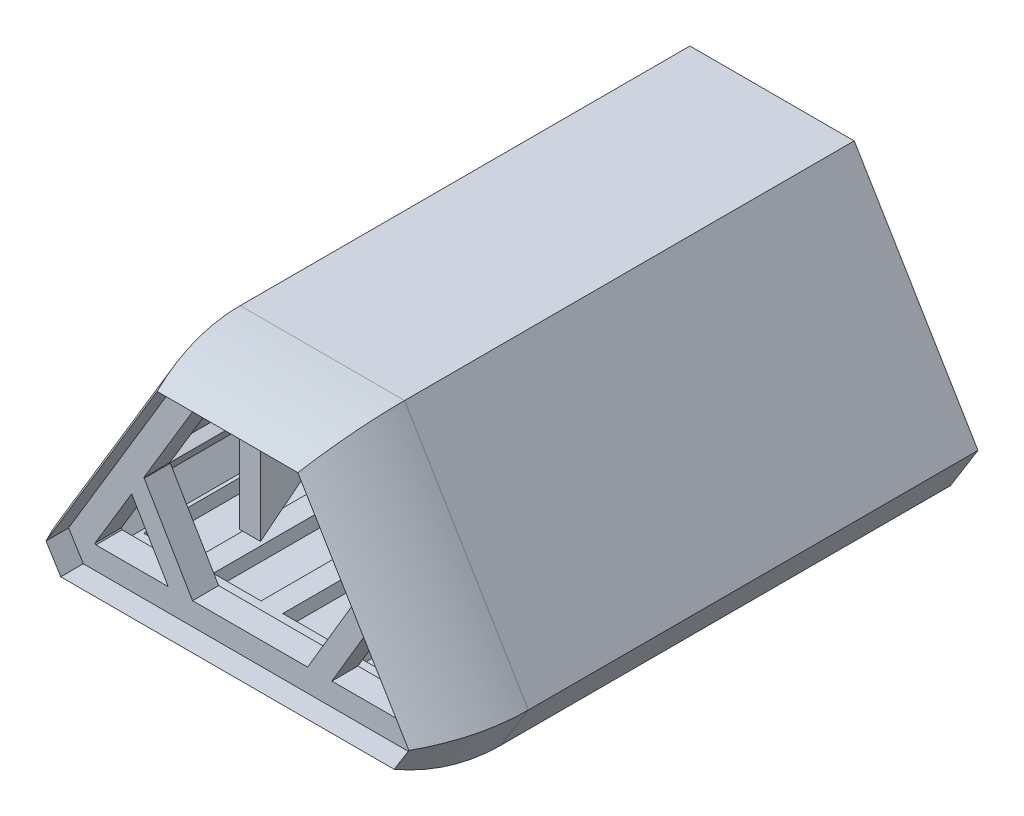
SolidWorks part; units mm, degrees
ref_plane "Front Plane" through (0, 0, 0) normal (0, 0, 1) x (1, 0, 0)
ref_plane "Top Plane" through (0, 0, 0) normal (0, 1, 0) x (1, 0, 0)
ref_plane "Right Plane" through (0, 0, 0) normal (1, 0, 0) x (0, 0, -1)
sketch "Sketch1" plane through (0, 0, 0) normal (0, 0, 1) x (1, 0, 0)
  line L0 (-24.4756, -10.0139) -> (-21.1802, -15.312)
  line L1 (-21.4286, -9.9899) -> (-19.7355, -12.712)
  line L2 (-19.7355, -12.712) -> (18.5963, -12.712)
  line L3 (18.5963, -12.712) -> (20.2895, -9.9899)
  line L4 (20.2895, -9.9899) -> (7.5154, 11.288)
  line L5 (7.5154, 11.288) -> (-8.6546, 11.288)
  line L6 (-8.6546, 11.288) -> (-21.4286, -9.9899)
  line L7 (-21.1802, -15.312) -> (20.041, -15.312)
  line L8 (20.041, -15.312) -> (23.3365, -10.0139)
  line L9 (23.3365, -10.0139) -> (8.9871, 13.888)
  line L10 (8.9871, 13.888) -> (-10.1263, 13.888)
  line L11 (-10.1263, 13.888) -> (-24.4756, -10.0139)
  dimension "D1" = 2.6
extrude "Boss-Extrude1" add sketch "Sketch1" along normal blind 62.6
sketch "Sketch2" plane through (0, 0, 62.6) normal (0, 0, 1) x (1, 0, 0)
  line L6 (-8.6546, 11.288) -> (-21.4286, -9.9899)
  line L7 (-21.4286, -9.9899) -> (-19.7355, -12.712)
  line L8 (-19.7355, -12.712) -> (18.5963, -12.712)
  line L9 (18.5963, -12.712) -> (20.2895, -9.9899)
  line L10 (20.2895, -9.9899) -> (7.5154, 11.288)
  line L11 (7.5154, 11.288) -> (-8.6546, 11.288)
  line L12 (-7.1829, 8.688) -> (-18.3817, -9.9658)
  line L13 (-18.3817, -9.9658) -> (-18.2908, -10.112)
  line L14 (-18.2908, -10.112) -> (17.1516, -10.112)
  line L15 (17.1516, -10.112) -> (17.2425, -9.9658)
  line L16 (17.2425, -9.9658) -> (6.0438, 8.688)
  line L17 (6.0438, 8.688) -> (-7.1829, 8.688)
  line L18 (-7.1829, 8.688) -> (-18.3817, -9.9658)
  line L19 (-18.3817, -9.9658) -> (-18.2908, -10.112)
  line L20 (-18.2908, -10.112) -> (17.1516, -10.112)
  line L21 (17.1516, -10.112) -> (17.2425, -9.9658)
  line L22 (17.2425, -9.9658) -> (6.0438, 8.688)
  line L23 (6.0438, 8.688) -> (-7.1829, 8.688)
  dimension "D1" = 2.6
  dimension "D2" = 2.6
extrude "Boss-Extrude2" add sketch "Sketch2" against normal blind 5.6
sketch "Sketch4" plane through (0, 0, 62.6) normal (0, 0, 1) x (1, 0, 0)
  line L21 (6.0438, 8.688) -> (-7.1829, 8.688)
  line L22 (-7.1829, 8.688) -> (-18.3817, -9.9658)
  line L23 (-18.3817, -9.9658) -> (-18.2908, -10.112)
  line L24 (-18.2908, -10.112) -> (17.1516, -10.112)
  line L25 (17.1516, -10.112) -> (17.2425, -9.9658)
  line L26 (17.2425, -9.9658) -> (6.0438, 8.688)
  line L27 (7.5154, 11.288) -> (-8.6546, 11.288)
  line L28 (20.2895, -9.9899) -> (7.5154, 11.288)
  line L29 (18.5963, -12.712) -> (20.2895, -9.9899)
  line L30 (-19.7355, -12.712) -> (18.5963, -12.712)
  line L31 (-21.4286, -9.9899) -> (-19.7355, -12.712)
  line L32 (-8.6546, 11.288) -> (-21.4286, -9.9899)
  line L33 (7.5154, 11.288) -> (-8.6546, 11.288)
  line L34 (20.2895, -9.9899) -> (7.5154, 11.288)
  line L35 (18.5963, -12.712) -> (20.2895, -9.9899)
  line L36 (-19.7355, -12.712) -> (18.5963, -12.712)
  line L37 (-21.4286, -9.9899) -> (-19.7355, -12.712)
  line L38 (-8.6546, 11.288) -> (-21.4286, -9.9899)
  dimension "D1" = 2.6
  dimension "D2" = 2.6
extrude "Cut-Extrude1" cut sketch "Sketch4" against normal blind 2.6
chamfer "Chamfer1" distance 5 distance2 2.6 6 edges at (-22.8279, -12.6629, 62.6) (-0.5696, -15.312, 62.6) (21.6887, -12.6629, 62.6) (16.1618, 1.9371, 62.6) (-0.5696, 13.888, 62.6) (-17.3009, 1.9371, 62.6) first distance on face at (-22.8279, -12.6629, 31.3) first distance on face at (-0.5696, -15.312, 31.3) first distance on face at (21.6887, -12.6629, 31.3) first distance on face at (16.1618, 1.9371, 31.3) first distance on face at (-0.5696, 13.888, 31.3) first distance on face at (-17.3009, 1.9371, 31.3)
sketch "Sketch7" plane through (0, 0, 60) normal (0, 0, 1) x (1, 0, 0)
  line L0 (-1.7696, 11.288) -> (-1.7696, -0.312)
  line L1 (-1.7696, 11.288) -> (0.6304, 11.288)
  line L2 (7.5154, 11.288) -> (-8.6546, 11.288) construction
  line L3 (-1.7696, -0.312) -> (0.6304, -0.312)
  line L4 (0.6304, -0.312) -> (0.6304, 11.288)
  point P9 (-0.5696, -0.312)
  dimension "D1" = 11.6
extrude "Boss-Extrude3" add sketch "Sketch7" against normal blind 14.6
sketch "Sketch8" plane through (0.6304, 0, 0) normal (1, 0, 0) x (0, 0, -1)
  line L0 (-45.4, -0.312) -> (-45.4, 11.288)
  line L1 (-45.4, -0.312) -> (-60, -0.312) construction
  line L2 (-45.4, -0.312) -> (-45.4, 11.288) construction
  line L3 (-45.4, 11.288) -> (-60, -0.312)
  line L4 (-60, 8.688) -> (-60, -9.9658) construction
  line L5 (-60, -0.312) -> (-45.4, -0.312)
extrude "Cut-Extrude2" cut sketch "Sketch8" against normal blind 5.6
sketch "Sketch9" plane through (0, 0, 60) normal (0, 0, 1) x (1, 0, 0)
  line L0 (13.0469, -2.9772) -> (8.8314, -10.112)
  line L1 (-14.1861, -2.9772) -> (-14.8224, -2.5851)
  line L2 (-18.2908, -10.112) -> (17.1516, -10.112) construction
  line L3 (-12.7368, -0.712) -> (-7.1829, -10.112)
  line L4 (11.6431, -0.6389) -> (6.0438, -10.112)
  line L5 (-9.9705, -10.112) -> (-14.1861, -2.9772)
  line L6 (-14.8224, -2.5851) -> (-13.3476, -0.1914)
  line L7 (-7.1829, 8.688) -> (-18.3817, -9.9658) construction
  line L8 (-13.3476, -0.1914) -> (-12.7368, -0.712)
  line L9 (-9.9705, -10.112) -> (-9.9705, -10.7546)
  line L10 (-9.9705, -10.7546) -> (-6.6285, -10.7546)
  line L11 (17.2425, -9.9658) -> (6.0438, 8.688) construction
  line L12 (-6.6285, -10.7546) -> (-7.1829, -10.112)
  line L13 (8.8314, -10.112) -> (9.2111, -10.7546)
  line L14 (9.2111, -10.7546) -> (5.8074, -10.7546)
  line L15 (5.8074, -10.7546) -> (6.0438, -10.112)
  line L16 (13.0469, -2.9772) -> (13.7146, -2.3095)
  line L17 (13.7146, -2.3095) -> (11.9023, -0.4971)
  line L18 (11.9023, -0.4971) -> (11.6431, -0.6389)
extrude "Boss-Extrude11" add sketch "Sketch9" against normal blind 3
sketch "Sketch10" plane through (0, 0, 0) normal (0, 0, -1) x (-1, 0, 0)
  line L12 (24.4756, -10.0139) -> (10.1263, 13.888)
  line L13 (10.1263, 13.888) -> (-8.9871, 13.888)
  line L14 (-8.9871, 13.888) -> (-23.3365, -10.0139)
  line L15 (-23.3365, -10.0139) -> (-20.041, -15.312)
  line L16 (-20.041, -15.312) -> (21.1802, -15.312)
  line L17 (21.1802, -15.312) -> (24.4756, -10.0139)
  line L18 (24.4756, -10.0139) -> (10.1263, 13.888)
  line L19 (10.1263, 13.888) -> (-8.9871, 13.888)
  line L20 (-8.9871, 13.888) -> (-23.3365, -10.0139)
  line L21 (-23.3365, -10.0139) -> (-20.041, -15.312)
  line L22 (-20.041, -15.312) -> (21.1802, -15.312)
  line L23 (21.1802, -15.312) -> (24.4756, -10.0139)
  line L30 (24.2412, -10.0121) -> (10.0131, 13.688)
  line L31 (10.0131, 13.688) -> (-8.8739, 13.688)
  line L32 (-8.8739, 13.688) -> (-23.1021, -10.0121)
  line L33 (-23.1021, -10.0121) -> (-19.9299, -15.112)
  line L34 (-19.9299, -15.112) -> (21.069, -15.112)
  line L35 (21.069, -15.112) -> (24.2412, -10.0121)
  line L36 (24.2412, -10.0121) -> (10.0131, 13.688)
  line L37 (10.0131, 13.688) -> (-8.8739, 13.688)
  line L38 (-8.8739, 13.688) -> (-23.1021, -10.0121)
  line L39 (-23.1021, -10.0121) -> (-19.9299, -15.112)
  line L40 (-19.9299, -15.112) -> (21.069, -15.112)
  line L41 (21.069, -15.112) -> (24.2412, -10.0121)
  dimension "D1" = 0
  dimension "D2" = 0.2
extrude "Cut-Extrude3" cut sketch "Sketch10" against normal blind 81
fillet "Fillet1" radius 26 6 edges at (21.516, -12.562, 57.9846) (-0.5696, -15.112, 57.9846) (-22.6551, -12.562, 57.9846) (-17.1271, 1.838, 57.9846) (-0.5696, 13.688, 57.9846) (15.988, 1.838, 57.9846)
sketch "Sketch11" plane through (0, -12.712, 0) normal (0, 1, 0) x (1, 0, 0)
  line L5 (-3.3196, -53.4909) -> (2.1804, -53.4909)
  line L6 (-3.3196, -53.4909) -> (-3.3196, -2.4909)
  line L7 (-3.3196, -2.4909) -> (2.1804, -2.4909)
  line L8 (2.1804, -53.4909) -> (2.1804, -2.4909)
  line L9 (-3.3196, -53.4909) -> (2.1804, -2.4909) construction
  line L10 (-3.3196, -2.4909) -> (2.1804, -53.4909) construction
  point P8 (-0.5696, -27.9909)
  dimension "D2" = 5.5
  dimension "D3" = 51
extrude "Cut-Extrude4" cut sketch "Sketch11" against normal blind 1.6
pattern_linear "LPattern1" count 3 spacing 8 along (1, 0, 0) count 3 spacing 8 along (-1, 0, 0) of "Cut-Extrude4"
sketch "Sketch12" plane through (-11.3431, 6.8097, 0) normal (0.8574, -0.5147, 0) x (0, 0, -1)
  line L0 (0, -7.1856) -> (-57, -7.1856) construction
  line L1 (0, 5.2233) -> (0, -19.5945) construction
  line L2 (-57, 5.2233) -> (-57, -19.5945) construction
  line L3 (-53.4909, -9.614) -> (-53.4909, -4.7572)
  line L4 (-53.4909, -4.7572) -> (-2.4909, -4.7572)
  line L6 (-53.4909, -9.614) -> (-2.4909, -9.614)
  line L7 (-2.4909, -4.7572) -> (-2.4909, -9.614)
  line L8 (-53.4909, -4.8523) -> (-2.4909, -9.614) construction
  line L9 (-53.4909, -9.519) -> (-2.4909, -4.7572) construction
  point P6 (-28.5, -7.1856)
extrude "Cut-Extrude5" cut sketch "Sketch12" against normal blind 1.6
pattern_linear "LPattern2" count 2 spacing 8 along (-0.5147, -0.8574, 0) count 2 spacing 8 along (0.5147, 0.8574, 0) of "Cut-Extrude5"
sketch "Sketch13" plane through (10.5057, 6.307, 0) normal (-0.8574, -0.5147, 0) x (0, 0, 1)
  line L0 (0, -6.5993) -> (57, -6.5993) construction
  line L1 (0, -19.0082) -> (0, 5.8097) construction
  line L2 (57, -19.0082) -> (57, 5.8097) construction
  line L3 (53.4909, -9.3493) -> (53.4909, -3.8493)
  line L4 (53.4909, -3.8493) -> (2.4909, -3.8493)
  line L6 (53.4909, -9.3493) -> (2.4909, -9.3493)
  line L7 (2.4909, -3.8493) -> (2.4909, -9.3493)
  line L8 (53.4909, -3.9569) -> (2.4909, -9.3493) construction
  line L9 (53.4909, -9.2416) -> (2.4909, -3.8493) construction
  point P6 (28.5, -6.5993)
  dimension "D1" = 5.5
extrude "Cut-Extrude6" cut sketch "Sketch13" against normal blind 1.6
pattern_linear "LPattern3" count 2 spacing 8 along (0.5147, -0.8574, 0) count 2 spacing 8 along (-0.5147, 0.8574, 0) of "Cut-Extrude6"
sketch "Sketch14" plane through (0, 11.288, 0) normal (0, -1, 0) x (1, 0, 0)
  line L2 (6.8804, 53.5494) -> (1.3804, 53.5494)
  line L4 (1.3804, 53.5494) -> (1.3804, 2.5494)
  line L5 (1.3804, 2.5494) -> (6.8804, 2.5494)
  line L6 (6.8804, 53.5494) -> (6.8804, 2.5494)
  line L7 (1.6964, 53.5494) -> (6.8804, 2.5494) construction
  line L8 (1.3804, 2.5494) -> (6.5645, 53.5494) construction
  line L10 (-2.5604, 53.5615) -> (-8.0604, 53.5615)
  line L11 (-8.0604, 53.5615) -> (-8.0604, 2.5615)
  line L12 (-8.0604, 2.5615) -> (-2.5604, 2.5615)
  line L13 (-2.5604, 53.5615) -> (-2.5604, 2.5615)
  line L14 (-7.7444, 53.5615) -> (-2.5604, 2.5615) construction
  line L15 (-8.0604, 2.5615) -> (-2.8763, 53.5615) construction
  point P4 (4.1304, 29.6036)
  point P16 (-5.3104, 29.6157)
extrude "Cut-Extrude7" cut sketch "Sketch14" against normal blind 1.6
chamfer "Chamfer2" distance 1.7 angle 50 1 edges at (-0.5696, -12.712, 57) first distance on face at (-15.2073, -8.2917, 57)
chamfer "Chamfer3" distance 1.7 angle 50 1 edges at (-15.0416, 0.6491, 57) first distance on face at (-15.2073, -8.2917, 57)
chamfer "Chamfer4" distance 1.7 angle 50 1 edges at (13.9025, 0.6491, 57) first distance on face at (-15.2073, -8.2917, 57)
